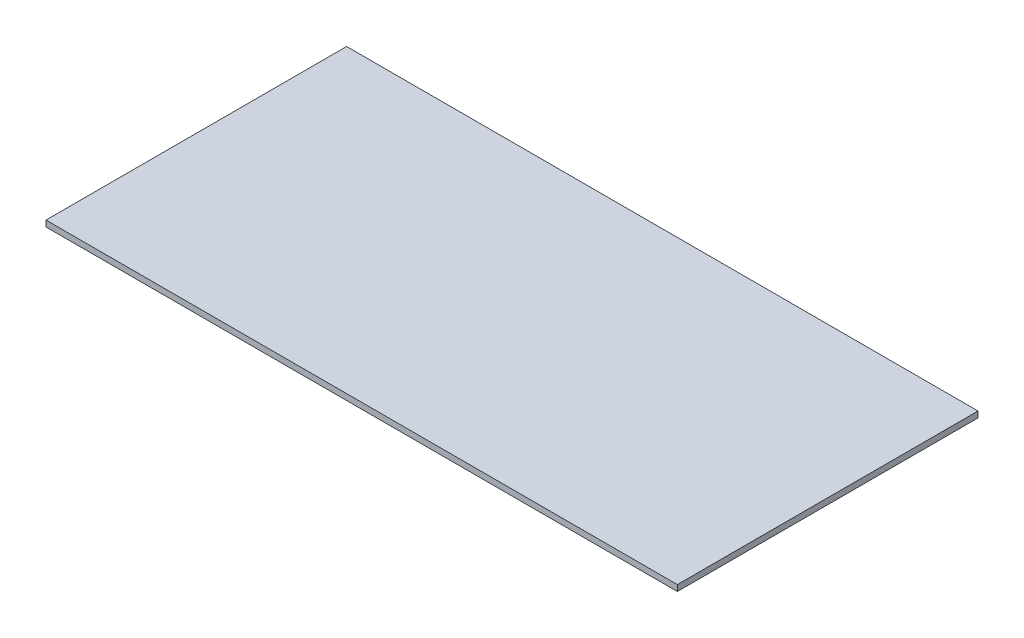
SolidWorks part; units mm, degrees
ref_plane "Спереди" through (0, 0, 0) normal (0, 0, 1) x (1, 0, 0)
ref_plane "Сверху" through (0, 0, 0) normal (0, 1, 0) x (1, 0, 0)
ref_plane "Справа" through (0, 0, 0) normal (1, 0, 0) x (0, 0, -1)
sketch "Эскиз1" plane through (0, 0, 0) normal (0, 1, 0) x (1, 0, 0)
  line L5 (0, 0) -> (210, 0)
  line L6 (0, 0) -> (0, 100)
  line L7 (0, 100) -> (210, 100)
  line L8 (210, 0) -> (210, 100)
  dimension "D1" = 210
  dimension "D2" = 100
extrude "Бобышка-Вытянуть1" add sketch "Эскиз1" along normal blind 2
